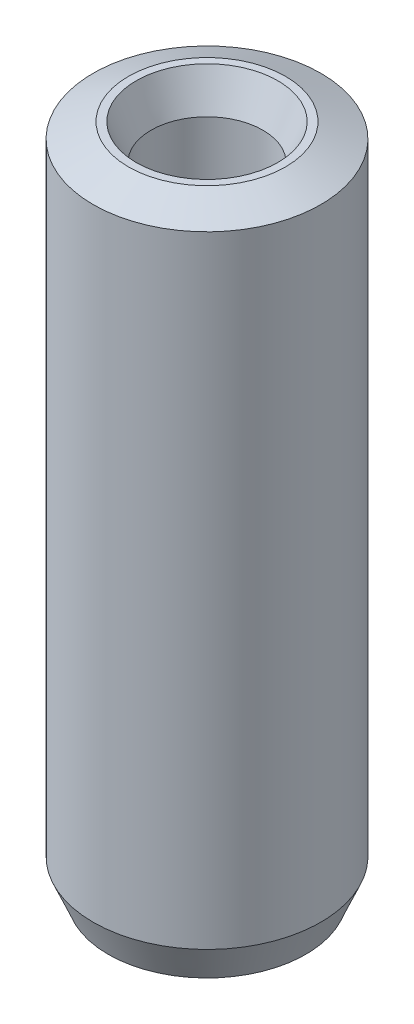
SolidWorks part; units mm, degrees
ref_plane "Front Plane" through (0, 0, 0) normal (0, 0, 1) x (1, 0, 0)
ref_plane "Top Plane" through (0, 0, 0) normal (0, 1, 0) x (1, 0, 0)
ref_plane "Right Plane" through (0, 0, 0) normal (1, 0, 0) x (0, 0, -1)
sketch "Sketch1" plane through (0, 0, 0) normal (0, 1, 0) x (1, 0, 0)
  circle A0 centre (0, 0) radius 5
  dimension "SLEEVE_OD" = 10
extrude "Boss-Extrude1" add sketch "Sketch1" along normal blind 29.51
sketch "Sketch2" plane through (0, 0, 0) normal (0, 1, 0) x (1, 0, 0)
  circle A0 centre (0, 0) radius 2.4557
  dimension "BORE_D" = 4.9115
extrude "Cut-Extrude1" cut sketch "Sketch2" along normal through all
chamfer "Chamfer1" distance 0.6573 angle 67.037 4 edges at (0, 29.51, 2.4557) (0, 0, 2.4557) (0, 0, 5) (0, 29.51, 5) first distance on face at (0, 29.51, 2.4557) first distance on face at (0, 0, 2.4557) first distance on face at (0, 29.51, 5)
